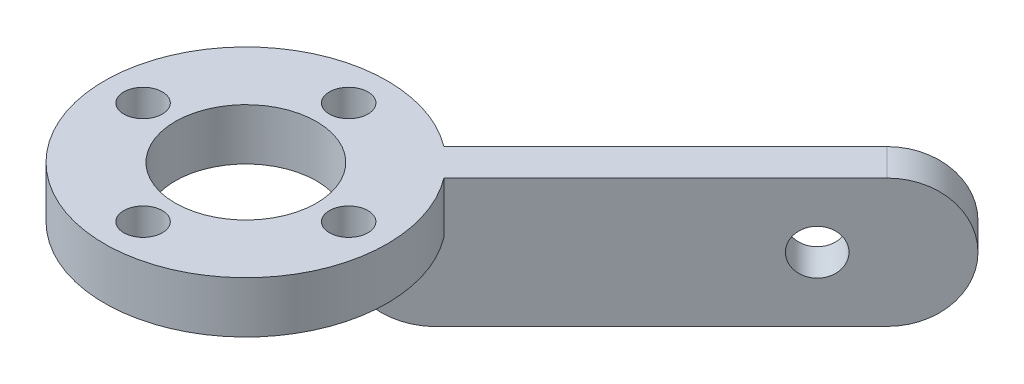
SolidWorks part; units mm, degrees
ref_plane "Alzado" through (0, 0, 0) normal (0, 0, 1) x (1, 0, 0)
ref_plane "Planta" through (0, 0, 0) normal (0, 1, 0) x (1, 0, 0)
ref_plane "Vista lateral" through (0, 0, 0) normal (1, 0, 0) x (0, 0, -1)
sketch "Croquis1" plane through (0, 0, 0) normal (0, 1, 0) x (1, 0, 0)
  line L0 (0, 0) -> (-14.1376, 0) construction
  circle A0 centre (0, 0) radius 11
  circle A1 centre (0, 0) radius 5.5
  circle A2 centre (-8, 0) radius 1.5
  circle A3 centre (0, 8) radius 1.5
  circle A4 centre (8, 0) radius 1.5
  circle A5 centre (0, -8) radius 1.5
  point P17 (0, 0)
  dimension "D1" = 22
  dimension "D2" = 11
  dimension "D3" = 8
  dimension "D4" = 3
  dimension "D5" = 4
extrude "Saliente-Extruir1" add sketch "Croquis1" along normal blind 4
sketch "Croquis2" plane through (0, 4, 0) normal (0, 1, 0) x (1, 0, 0)
  line L0 (0, 0) -> (26.3206, 26.3206) construction
  line L1 (0, 0) -> (0, 5.5) construction
  line L2 (2.681, 4.8023) -> (27.4297, 29.5511)
  line L3 (27.4297, 29.5511) -> (29.5511, 27.4297)
  line L4 (4.8023, 2.681) -> (29.5511, 27.4297)
  circle A0 centre (0, 0) radius 5.5 construction
  arc A1 (2.681, 4.8023) -> (4.8023, 2.681) centre (0.1188, 0.1188) cw
  point P12 (28.4904, 28.4904)
  dimension "D1" = 45
  dimension "D2" = 1.5
  dimension "D3" = 35
extrude "Saliente-Extruir2" add sketch "Croquis2" against normal blind 10
sketch "Croquis3" plane through (-1.0607, 0, -1.0607) normal (-0.7071, 0, -0.7071) x (-0.7071, 0, 0.7071)
  line L0 (-40.2915, -1) -> (-5.2915, -1) construction
  line L1 (-40.2915, -6) -> (-40.2915, 4) construction
  line L2 (-5.2915, -6) -> (-5.2915, 0) construction
  line L4 (-31.4415, 0.85) -> (-31.4415, -1) construction
  circle A0 centre (-31.4415, -1) radius 1.75
  dimension "D1" = 3.5
extrude "Cortar-Extruir1" cut sketch "Croquis3" against normal up to next
fillet "Redondeo1" radius 5 3 edges at (3.8937, -6, -3.8937) (28.4904, -6, -28.4904) (28.4904, 4, -28.4904)
